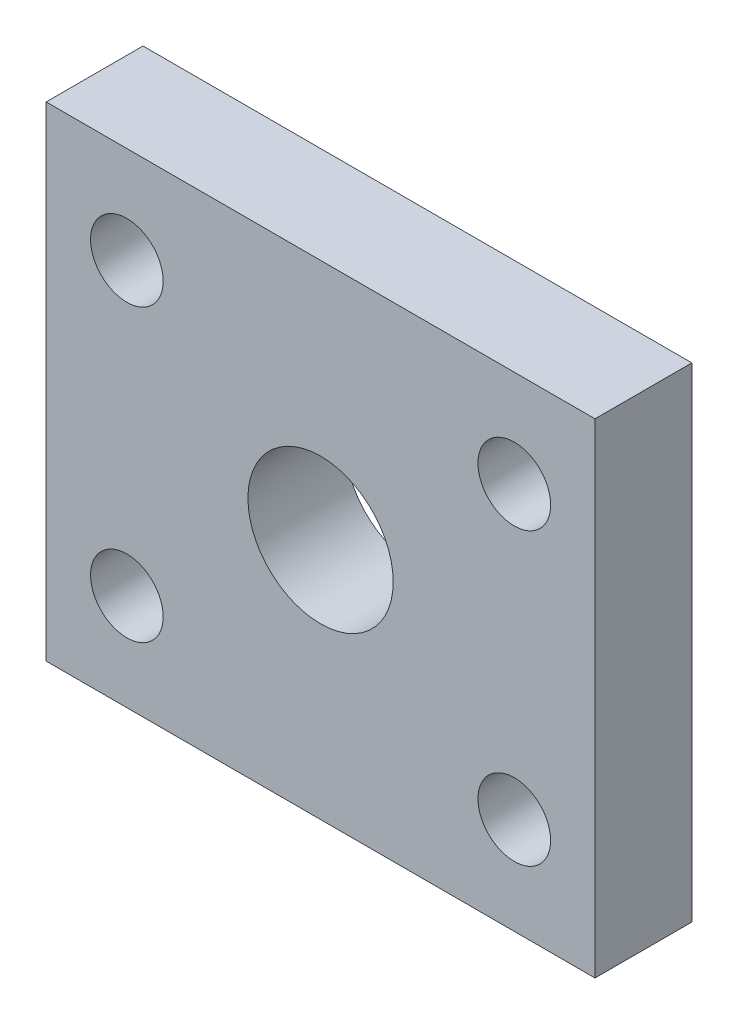
SolidWorks part; units mm, degrees
ref_plane "Front Plane" through (0, 0, 0) normal (0, 0, 1) x (1, 0, 0)
ref_plane "Top Plane" through (0, 0, 0) normal (0, 1, 0) x (1, 0, 0)
ref_plane "Right Plane" through (0, 0, 0) normal (1, 0, 0) x (0, 0, -1)
sketch "Sketch2" plane through (0, 0, 0) normal (0, 0, 1) x (1, 0, 0)
  line L1 (-17, 15) -> (17, 15)
  line L2 (-17, 15) -> (-17, -15)
  line L3 (-17, -15) -> (17, -15)
  line L4 (17, 15) -> (17, -15)
  line L5 (-17, 15) -> (17, -15) construction
  line L6 (-17, -15) -> (17, 15) construction
  point P0 (0, 0)
  dimension "D1" = 34
  dimension "D2" = 30
extrude "Boss-Extrude1" add sketch "Sketch2" along normal blind 6
sketch "Sketch3" plane through (0, 0, 0) normal (0, 0, -1) x (-1, 0, 0)
  line L0 (0, 15) -> (0, -15) construction
  line L1 (-17, 15) -> (17, 15) construction
  line L2 (17, -15) -> (-17, -15) construction
  line L3 (-17, 0) -> (17, 0) construction
  line L4 (-17, -15) -> (-17, 15) construction
  line L5 (17, 15) -> (17, -15) construction
  circle A0 centre (-12, 9) radius 2.25
  circle A1 centre (12, 9) radius 2.25
  circle A2 centre (12, -9) radius 2.25
  circle A3 centre (-12, -9) radius 2.25
  dimension "D1" = 4.5
  dimension "D2" = 6
  dimension "D3" = 5
extrude "Cut-Extrude1" cut sketch "Sketch3" against normal blind 10
sketch "Sketch4" plane through (0, 0, 0) normal (0, 0, -1) x (-1, 0, 0)
  circle A1 centre (0, 0) radius 4.5
  dimension "D2" = 9
extrude "Cut-Extrude2" cut sketch "Sketch4" against normal blind 10
